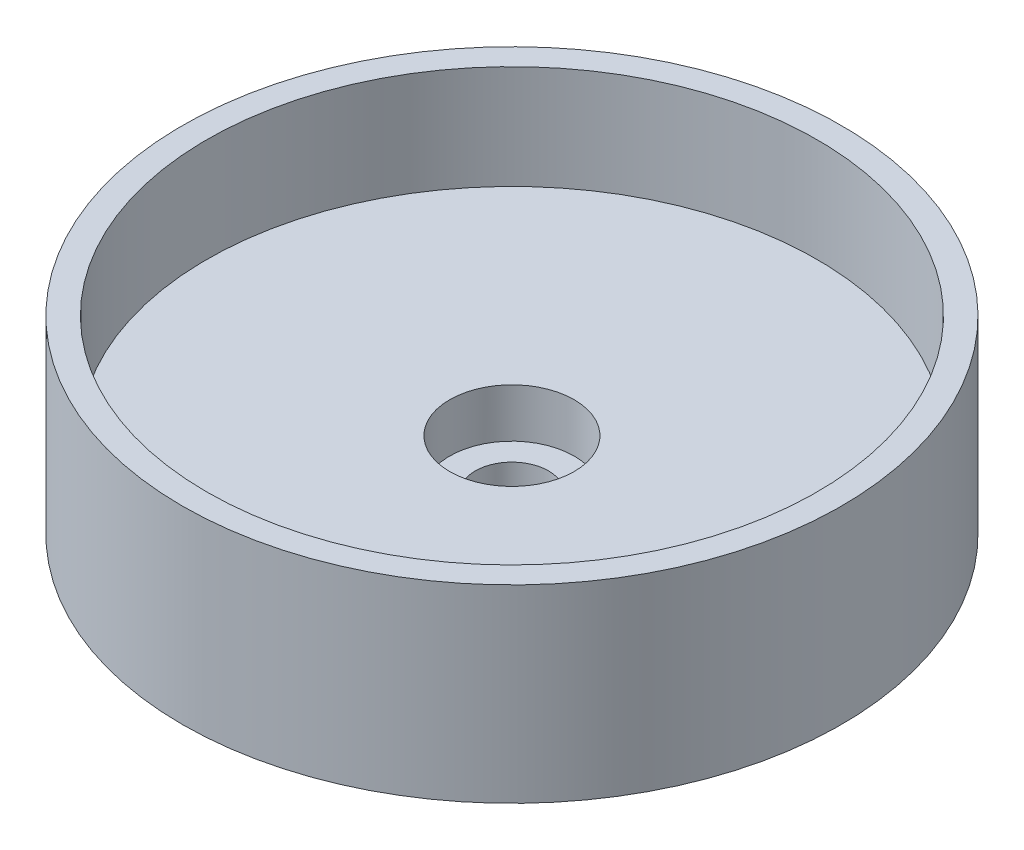
SolidWorks part; units mm, degrees
ref_plane "Plan de face" through (0, 0, 0) normal (0, 0, 1) x (1, 0, 0)
ref_plane "Plan de dessus" through (0, 0, 0) normal (0, 1, 0) x (1, 0, 0)
ref_plane "Plan de droite" through (0, 0, 0) normal (1, 0, 0) x (0, 0, -1)
sketch "Esquisse1" plane through (0, 0, 0) normal (0, 1, 0) x (1, 0, 0)
  circle A0 centre (0, 0) radius 5.1
  circle A1 centre (0, 0) radius 25
  dimension "D1" = 10.2
  dimension "D2" = 50
extrude "Boss.-Extru.1" add sketch "Esquisse1" along normal blind 7
sketch "Esquisse2" plane through (0, 0, 0) normal (0, -1, 0) x (1, 0, 0)
  circle A0 centre (0, 0) radius 3
  circle A1 centre (0, 0) radius 25
  circle A2 centre (0, 0) radius 25 construction
  dimension "D1" = 6
extrude "Boss.-Extru.2" add sketch "Esquisse2" against normal blind 3
sketch "Esquisse3" plane through (0, 7, 0) normal (0, 1, 0) x (1, 0, 0)
  circle A0 centre (0, 0) radius 27
  circle A1 centre (0, 0) radius 25
  circle A2 centre (0, 0) radius 25 construction
  dimension "D1" = 2
extrude "Boss.-Extru.3" add sketch "Esquisse3" along normal blind 8.5 and the other way up to surface (7 mm away) other way up to face at (0, 0, 25)
ref_axis "Axe1" through (0, 3, 0) along (0, -1, 0)
